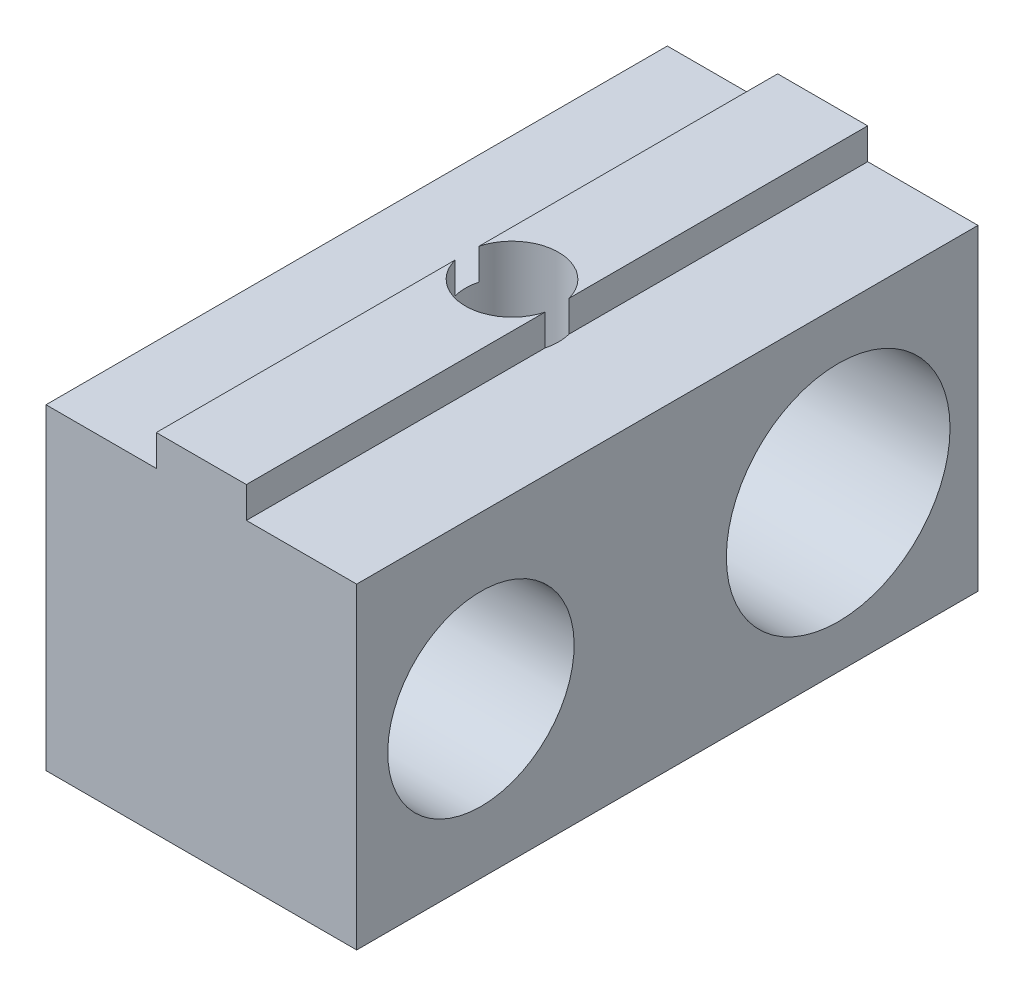
SolidWorks part; units mm, degrees
ref_plane "Front Plane" through (0, 0, 0) normal (0, 0, 1) x (1, 0, 0)
ref_plane "Top Plane" through (0, 0, 0) normal (0, 1, 0) x (1, 0, 0)
ref_plane "Right Plane" through (0, 0, 0) normal (1, 0, 0) x (0, 0, -1)
sketch "Sketch1" plane through (0, 0, 0) normal (0, 0, 1) x (1, 0, 0)
  line L0 (-5, 0) -> (5, 0)
  line L1 (5, 0) -> (5, 0.2)
  line L2 (5, 0.2) -> (1.45, 0.2)
  line L3 (1.45, 0.2) -> (1.45, 1.2)
  line L4 (1.45, 1.2) -> (-1.45, 1.2)
  line L5 (-1.45, 1.2) -> (-1.45, 0.2)
  line L6 (-1.45, 0.2) -> (-5, 0.2)
  line L7 (-5, 0.2) -> (-5, 0)
  point P9 (0, 0)
  dimension "D1" = 10
  dimension "D2" = 2.9
  dimension "D3" = 0.2
  dimension "D4" = 1
extrude "MakerBeamFix" add sketch "Sketch1" along normal mid plane 20
sketch "Sketch3" plane through (-5, 0, 0) normal (-1, 0, 0) x (0, 0, 1)
  line L1 (10, -10) -> (-10, -10)
  line L2 (10, -10) -> (10, 0)
  line L3 (10, 0) -> (-10, 0)
  line L4 (-10, -10) -> (-10, 0)
  line L5 (10, -10) -> (-10, 0) construction
  line L6 (10, 0) -> (-10, -10) construction
  line L7 (-10, 0.2) -> (-10, 0) construction
  line L8 (-10, 1.2) -> (-10, 0.2) construction
  line L9 (10, 0) -> (-10, 0) construction
  circle A0 centre (6, -5) radius 3
  circle A1 centre (-5.5, -5) radius 3.6
  point P8 (0, -5)
  point P9 (0, 0)
  point P10 (12.5, 0)
  point P11 (-11, 0)
  point P12 (-11, 3)
  point P13 (0, 0)
  point P14 (12.5, 0)
  point P16 (10, 0)
  point P21 (-11, 0)
  point P24 (11, 0)
  dimension "D1" = 7.2
  dimension "D4" = 6
  dimension "D3" = 10
  dimension "D5" = 4
  dimension "D6" = 4.5
extrude "DrillKeyAndSmallHexDriver" add sketch "Sketch3" against normal blind 10
sketch "Sketch4" plane through (0, -10, 0) normal (0, -1, 0) x (1, 0, 0)
  line L0 (-5, -10) -> (-5, 10) construction
  circle A0 centre (0, 0) radius 1.5
  point P5 (-5, 0)
  dimension "D1" = 3
  dimension "D2" = 5
extrude "FixingHole" cut sketch "Sketch4" against normal through all
ref_plane "Plane1" through (0, -7.8, 0) normal (0, 1, 0) x (1, 0, 0)
sketch "Sketch5" plane through (0, -7.8, 0) normal (0, 1, 0) x (1, 0, 0)
  circle A0 centre (0, 0) radius 4.25
  dimension "D1" = 8.5
extrude "DriverHole" cut sketch "Sketch5" against normal through all
